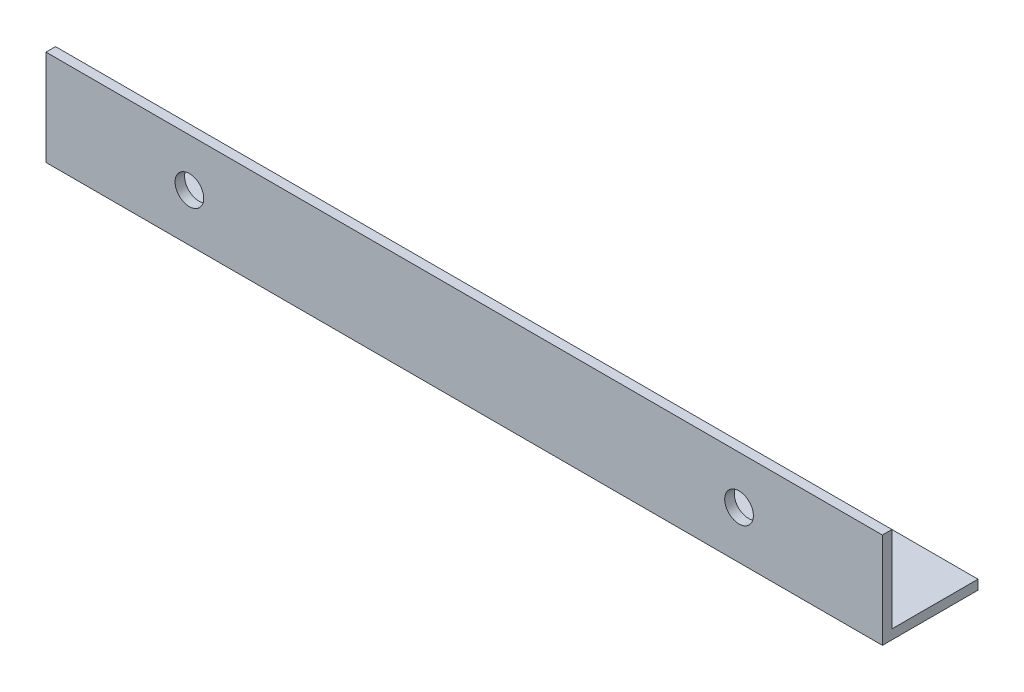
SolidWorks part; units mm, degrees
ref_plane "Front Plane" through (0, 0, 0) normal (0, 0, 1) x (1, 0, 0)
ref_plane "Top Plane" through (0, 0, 0) normal (0, 1, 0) x (1, 0, 0)
ref_plane "Right Plane" through (0, 0, 0) normal (1, 0, 0) x (0, 0, -1)
sketch "Эскиз1" plane through (0, 0, 0) normal (1, 0, 0) x (0, 0, -1)
  line L0 (0, 0) -> (0, 40)
  line L1 (0, 40) -> (4, 40)
  line L2 (4, 40) -> (4, 4)
  line L3 (4, 4) -> (40, 4)
  line L4 (40, 4) -> (40, 0)
  line L5 (40, 0) -> (0, 0)
  dimension "D1" = 40
  dimension "D2" = 40
  dimension "D3" = 4
  dimension "D4" = 4
extrude "Бобышка-Вытянуть1" add sketch "Эскиз1" along normal blind 350
sketch "Эскиз2" plane through (0, 0, 0) normal (0, 0, 1) x (1, 0, 0)
  line L0 (0, 40) -> (0, 0) construction
  line L1 (350, 40) -> (0, 40) construction
  circle A0 centre (60, 20) radius 6
  dimension "D1" = 12
  dimension "D2" = 60
  dimension "D3" = 20
extrude "Вырез-Вытянуть1" cut sketch "Эскиз2" against normal through all
sketch "Эскиз3" plane through (0, 0, 0) normal (0, 0, 1) x (1, 0, 0)
  line L0 (350, 40) -> (0, 40) construction
  line L1 (350, 40) -> (350, 0) construction
  circle A0 centre (290, 20) radius 6
  dimension "D1" = 20
  dimension "D2" = 60
extrude "Вырез-Вытянуть2" cut sketch "Эскиз3" against normal through all
